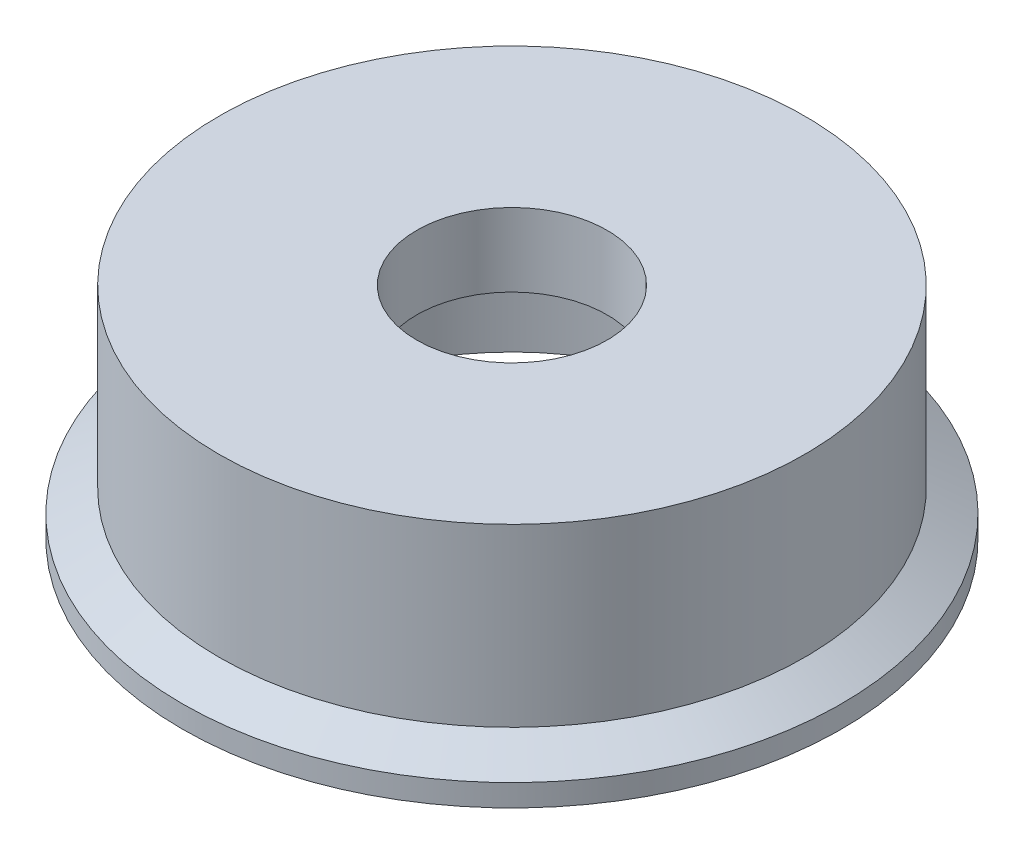
SolidWorks part; units mm, degrees
ref_plane "Front Plane" through (0, 0, 0) normal (0, 0, 1) x (1, 0, 0)
ref_plane "Top Plane" through (0, 0, 0) normal (0, 1, 0) x (1, 0, 0)
ref_plane "Right Plane" through (0, 0, 0) normal (1, 0, 0) x (0, 0, -1)
sketch "Sketch1" plane through (0, 0, 0) normal (0, 0, 1) x (1, 0, 0)
  line L0 (0, 7.62) -> (0, 0) construction
  line L1 (0, -55) -> (0, 55) construction
  line L2 (-3.302, 7.62) -> (-10.16, 7.62)
  line L3 (-10.16, 7.62) -> (-10.16, 1.524)
  line L4 (-10.16, 1.524) -> (-11.43, 0.762)
  line L5 (-11.43, 0.762) -> (-11.43, 0)
  line L6 (55, 0) -> (-55, 0) construction
  line L7 (-11.43, 0) -> (-7.9375, 0)
  line L8 (-7.9375, 0) -> (-7.9375, 5.08)
  line L9 (-7.9375, 5.08) -> (-3.302, 5.08)
  line L11 (-3.302, 7.62) -> (-3.302, 5.08)
  point P14 (-3.175, 5.08)
  point P16 (0, 7.62)
  point P17 (0, 0)
  point P18 (0, 0)
  point P19 (-10.16, 1.8049)
  dimension "D1" = 7.62
  dimension "D2" = 10.16
  dimension "D3" = 5.08
  dimension "D4" = 3.302
  dimension "D5" = 7.9375
  dimension "D6" = 0.762
  dimension "D7" = 1.27
  dimension "D8" = 1.524
revolve "Revolve1" add sketch "Sketch1" angle 360 about L0
